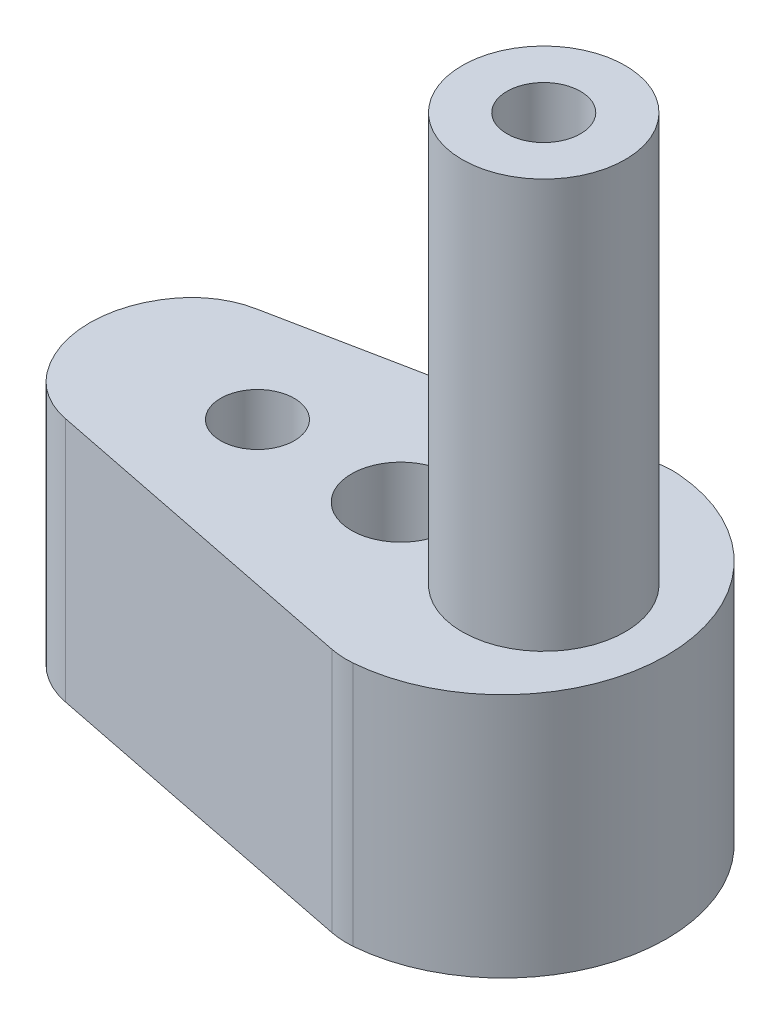
SolidWorks part; units mm, degrees
ref_plane "Front Plane" through (0, 0, 0) normal (0, 0, 1) x (1, 0, 0)
ref_plane "Top Plane" through (0, 0, 0) normal (0, 1, 0) x (1, 0, 0)
ref_plane "Right Plane" through (0, 0, 0) normal (1, 0, 0) x (0, 0, -1)
sketch "Sketch1" plane through (0, 0, 0) normal (0, 1, 0) x (1, 0, 0)
  line L0 (-0.1139, 1.9772) -> (-1.25, 1.7502)
  line L1 (-0.1139, -1.9772) -> (-1.25, -1.7502)
  line L4 (-1.25, -1.7502) -> (-4.1832, -1.1642)
  line L5 (-1.25, 1.7502) -> (-4.1832, 1.1642)
  circle A0 centre (0.5, 0) radius 0.9966
  circle A1 centre (-1.25, 0) radius 0.6
  arc A2 (0.1641, 1.9933) -> (0.1641, -1.9933) centre (0, 0) cw
  arc A3 (-0.1139, -1.9772) -> (0.1641, -1.9933) centre (0.0821, -0.9966) ccw
  arc A4 (-4.7783, 0.7954) -> (-4.7783, -0.7954) centre (-3.75, 0) ccw
  arc A5 (0.1641, 1.9933) -> (-0.1139, 1.9772) centre (0.0821, 0.9966) ccw
  arc A6 (-4.1832, 1.1642) -> (-4.7783, 0.7954) centre (-3.9873, 0.1835) ccw
  arc A7 (-4.1832, -1.1642) -> (-4.7783, -0.7954) centre (-3.9873, -0.1835) cw
  circle A8 centre (-3, 0) radius 0.45
  circle A9 centre (0.5, 0) radius 0.45
  point P12 (-3, 0)
  point P20 (0.5, 0)
extrude "Boss-Extrude1" add sketch "Sketch1" along normal blind 3 contours A2 A5 L0 L1 A3 A9 | A0 A9 region at (0.0292, 0, -1.9141) region at (-0.4684, 0, 0)
extrude "Boss-Extrude2" add sketch "Sketch1<22>" along normal blind 8 contours A0 A9 region at (-0.4684, 0, 0)
sketch "Sketch1<22>" plane through (0, 0, 0) normal (0, 1, 0) x (1, 0, 0) same geometry as "Sketch1"
